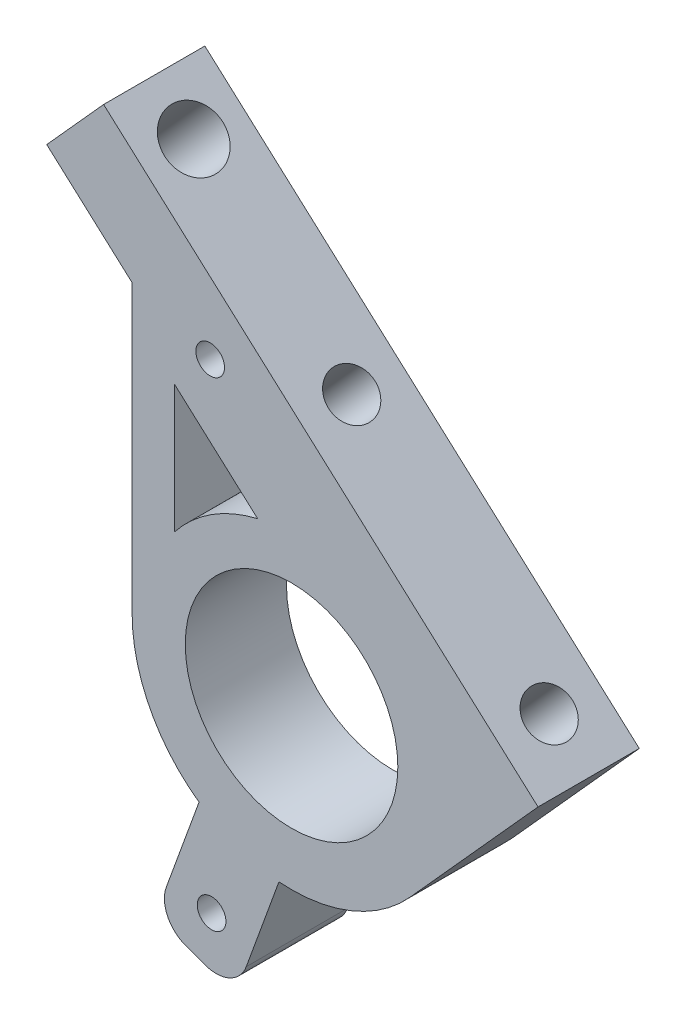
SolidWorks part; units mm, degrees
material "6061 Alloy"
ref_plane "Front Plane" through (0, 0, 0) normal (0, 0, 1) x (1, 0, 0)
ref_plane "Top Plane" through (0, 0, 0) normal (0, 1, 0) x (1, 0, 0)
ref_plane "Right Plane" through (0, 0, 0) normal (1, 0, 0) x (0, 0, -1)
sketch "Sketch1" plane through (0, 0, 0) normal (0, 0, 1) x (1, 0, 0)
  line L0 (-17.6814, 40.1418) -> (21.9261, 40.1418) construction
  line L1 (-15, 0) -> (-15, 26.9624)
  line L2 (-15, 26.9624) -> (-23.0345, 34.1967)
  line L3 (-23.0345, 34.1967) -> (-17.6814, 40.1418)
  line L4 (-17.6814, 40.1418) -> (23.1915, 3.3396)
  line L5 (23.1915, 3.3396) -> (17.8385, -2.6055)
  line L10 (17.8385, -2.6055) -> (11.1472, -10.037)
  line L11 (-15, 26.9624) -> (17.8385, -2.6055) construction
  circle A0 centre (0, 0) radius 10
  arc A1 (-15, 0) -> (11.1472, -10.037) centre (0, 0) ccw
  dimension "D3" = 20
  dimension "D4" = 5
  dimension "D1" = 42
  dimension "D2" = 8
  dimension "D7" = 55
extrude "3/8" add sketch "Sketch1" along normal blind 9.525
sketch "Sketch2" plane through (0, 0, 0) normal (0, 0, 1) x (1, 0, 0)
  line L0 (0, 0) -> (0, -7.8768) construction
  line L1 (-8.7033, -12.2169) -> (-1.1858, -14.9531)
  line L2 (-8.7033, -12.2169) -> (-12.8075, -23.4932)
  line L3 (-12.8075, -23.4932) -> (-5.29, -26.2294)
  line L4 (-1.1858, -14.9531) -> (-5.29, -26.2294)
  line L5 (-9.0488, -24.8613) -> (-4.9445, -13.585) construction
  line L6 (-10.7554, -17.8551) -> (-3.2379, -20.5912) construction
  arc A0 (-15, 0) -> (11.1472, -10.037) centre (0, 0) ccw construction
  point P360 (-6.9966, -19.2231)
  dimension "D1" = 12
  dimension "D2" = 8
  dimension "D3" = 110
extrude "Boss-Extrude2" add sketch "Sketch2" along normal up to surface (9.525 mm away) up to face at (-6.6377, 14.2697, 9.525)
sketch "Sketch3" plane through (0, 0, 9.525) normal (0, 0, 1) x (1, 0, 0)
  line L0 (0, 0) -> (-9.0488, -24.8613) construction
  line L1 (-12.8075, -23.4932) -> (-5.29, -26.2294) construction
  circle A0 centre (-7.5244, -20.6732) radius 1.35
  dimension "D2" = 2.7
  dimension "D1" = 22
extrude "M3_DRILL_or_Through" cut sketch "Sketch3" against normal up to surface (9.525 mm away) up to face at (-6.5272, 1.5509, 0)
fillet "Fillet1" radius 3 2 edges at (-5.29, -26.2294, 4.7625) (-12.8075, -23.4932, 4.7625)
sketch "Sketch4" plane through (12.0444, 13.3766, 0) normal (0.6691, 0.7431, 0) x (0.7431, -0.6691, 0)
  line L0 (-40, -4.7625) -> (15, -4.7625) construction
  line L1 (-40, -9.525) -> (-40, 0) construction
  line L2 (15, -9.525) -> (15, 0) construction
  circle A0 centre (-35, -4.7625) radius 2.75
  dimension "D2" = 5.5
  dimension "D1" = 5
extrude "M5_through" cut sketch "Sketch4" against normal up to surface (8 mm away) up to face at (-19.0172, 30.5795, 4.7625)
sketch "Sketch5" plane through (12.0444, 13.3766, 0) normal (0.6691, 0.7431, 0) x (0.7431, -0.6691, 0)
  line L0 (-35, -4.7625) -> (10, -4.7625) construction
  circle A0 centre (-15, -4.7625) radius 2.2
  circle A1 centre (10, -4.7625) radius 2.2
  dimension "D1" = 4.4
  dimension "D2" = 20
  dimension "D3" = 45
extrude "M5_DRILL" cut sketch "Sketch5" against normal blind 8
sketch "Sketch6" plane through (0, 0, 9.525) normal (0, 0, 1) x (1, 0, 0)
  line L0 (-11, 20.6695) -> (-11, 8.6603)
  line L1 (-11, 20.6695) -> (-3.185, 13.6329)
  line L2 (23.1915, 3.3396) -> (-17.6814, 40.1418) construction
  line L3 (-15, 26.9624) -> (-15, 0) construction
  arc A0 (-11, 8.6603) -> (-3.185, 13.6329) centre (0, 0) cw
  circle A1 centre (0, 0) radius 10 construction
  dimension "D3" = 4
  dimension "D1" = 10
  dimension "D2" = 4
extrude "Cut-Extrude4" cut sketch "Sketch6" against normal up to vertex (9.525 mm away) up to point (-17.6814, 40.1418, 0)
sketch "Sketch7" plane through (0, 0, 9.525) normal (0, 0, 1) x (1, 0, 0)
  line L0 (-11, 20.6695) -> (-4.3087, 28.101) construction
  line L1 (23.1915, 3.3396) -> (-17.6814, 40.1418) construction
  circle A0 centre (-7.6543, 24.3852) radius 1.35
  point P2 (0, 0)
  dimension "D1" = 2.7
extrude "M3_DRILL_or_Through2" cut sketch "Sketch7" against normal up to surface (9.525 mm away) up to face at (-8.5361, 14.5426, 0)
